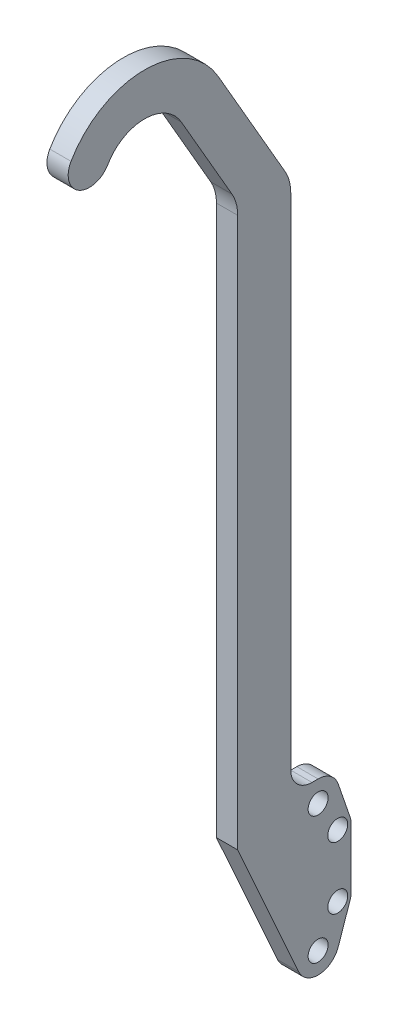
SolidWorks part; units mm, degrees
ref_plane "Front Plane" through (0, 0, 0) normal (0, 0, 1) x (1, 0, 0)
ref_plane "Top Plane" through (0, 0, 0) normal (0, 1, 0) x (1, 0, 0)
ref_plane "Right Plane" through (0, 0, 0) normal (1, 0, 0) x (0, 0, -1)
sketch "Sketch1" plane through (0, 0, 0) normal (1, 0, 0) x (0, 0, -1)
  line L0 (-8.7313, -21.6489) -> (-26.9875, 19.05)
  line L1 (-26.9875, 19.05) -> (-26.9875, 186.7592)
  line L2 (-26.9875, 186.7592) -> (-43.8119, 215.9)
  line L4 (-32.8134, 222.25) -> (-11.1125, 184.6629)
  line L5 (-11.1125, 184.6629) -> (-11.1125, 25.4)
  line L9 (-65.809, 215.9) -> (-69.3194, 209.8198) construction
  line L10 (-65.809, 210.2456) -> (-80.932, 184.0519) construction
  line L11 (-69.9334, 165.0019) -> (-39.6875, 165.0019) construction
  line L12 (-28.689, 184.0519) -> (-43.8119, 210.2456) construction
  line L13 (-7.9375, -87.9564) -> (7.9375, -87.9564) construction
  line L14 (-54.8105, 203.8956) -> (-69.9334, 177.7019) construction
  line L15 (-69.9334, 177.7019) -> (-39.6875, 177.7019) construction
  line L16 (-39.6875, 177.7019) -> (-54.8105, 203.8956) construction
  line L17 (-2.9375, -19.05) -> (-2.9375, 19.05) construction
  line L18 (7.9375, -87.9564) -> (7.9375, -76.9784) construction
  line L19 (-7.9375, -87.9564) -> (-7.9375, -76.9784) construction
  line L20 (-2.9375, 25.4) -> (-11.1125, 25.4)
  line L22 (3.0681, -21.1128) -> (6.691, -10.5649)
  line L23 (2.9375, -9.2757) -> (2.9375, 9.2757) construction
  line L24 (3.0681, 21.1128) -> (6.691, 10.5649)
  line L25 (6.9062, 9.2757) -> (6.9062, -9.2757)
  arc A2 (-43.8119, 215.9) -> (-65.809, 215.9) centre (-54.8105, 209.55) ccw
  arc A3 (-65.809, 215.9) -> (-76.8075, 222.25) centre (-71.3083, 219.075) cw
  arc A4 (-76.8075, 222.25) -> (-32.8134, 222.25) centre (-54.8105, 209.55) cw
  arc A7 (-43.8119, 210.2456) -> (-65.809, 210.2456) centre (-54.8105, 203.8956) ccw construction
  arc A9 (-80.932, 184.0519) -> (-69.9334, 165.0019) centre (-69.9334, 177.7019) ccw construction
  arc A10 (-39.6875, 165.0019) -> (-28.689, 184.0519) centre (-39.6875, 177.7019) ccw construction
  circle A11 centre (-54.8105, 186.4331) radius 8.7313 construction
  arc A12 (-8.7313, -21.6489) -> (3.0681, -21.1128) centre (-2.9375, -19.05) ccw
  arc A13 (6.691, -10.5649) -> (6.9062, -9.2757) centre (2.9375, -9.2757) ccw
  arc A14 (3.0681, 21.1128) -> (-2.9375, 25.4) centre (-2.9375, 19.05) ccw
  arc A15 (6.691, 10.5649) -> (6.9062, 9.2757) centre (2.9375, 9.2757) cw
  circle A16 centre (-2.9375, -19.05) radius 5.702 construction
  circle A17 centre (2.9375, -9.2757) radius 5.702 construction
  point P0 (0, -87.9564)
  point P2 (1.9375, 15.1051)
  point P3 (-2.9375, 19.05)
  point P4 (-2.9375, -19.05)
  point P14 (2.9375, -9.2757)
  point P21 (-2.9375, 0)
  point P48 (0, 0)
  point P50 (2.9375, 9.2757)
  point P51 (2.9375, 0)
  point P65 (-54.8105, 222.25)
  dimension "D2" = 38.1
  dimension "D3" = 15.875
  dimension "D10" = 222.25
  dimension "D11" = 12.7
  dimension "D13" = 12.7
  dimension "D15" = 11.1125
  dimension "D9" = 12.7
  dimension "D7" = 12.7
  dimension "D17" = 11.4041
  dimension "D18" = 7.9375
  dimension "D4" = 5
  dimension "D5" = 15.875
  dimension "D6" = 5
  dimension "D8" = 150
  dimension "D12" = 60
  dimension "D14" = 38.8937
  dimension "D16" = 38.1
extrude "Boss-Extrude1" add sketch "Sketch1" along normal mid plane 6.35
fillet "Fillet1" radius 12.7 2 edges at (0, 184.6629, 11.1125) (0, 186.7592, 26.9875)
sketch "Sketch2" plane through (3.175, 0, 0) normal (1, 0, 0) x (0, 0, -1)
  circle A0 centre (-2.9375, 19.05) radius 2.9845
  circle A1 centre (2.9375, -9.2757) radius 2.9845
  circle A2 centre (-2.9375, -19.05) radius 2.9845
  circle A3 centre (2.9375, 9.2757) radius 2.9845
  dimension "D1" = 5.969
extrude "Cut-Extrude1" cut sketch "Sketch2" against normal through all
fillet "Fillet2" radius 6.35 1 edges at (0, 25.4, 11.1125)
